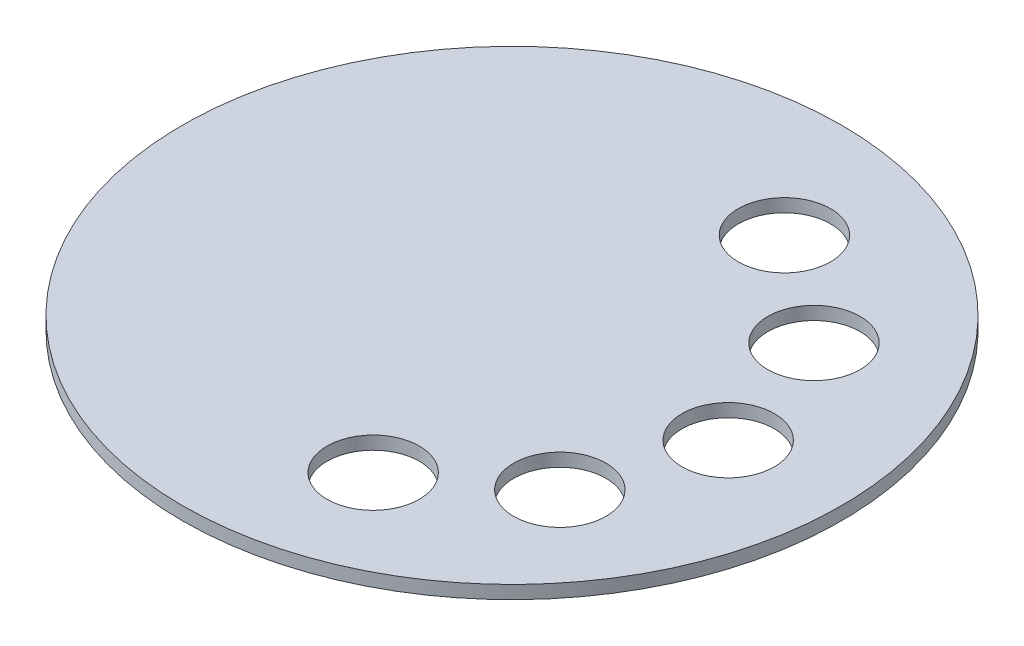
SolidWorks part; units mm, degrees
ref_plane "Front Plane" through (0, 0, 0) normal (0, 0, 1) x (1, 0, 0)
ref_plane "Top Plane" through (0, 0, 0) normal (0, 1, 0) x (1, 0, 0)
ref_plane "Right Plane" through (0, 0, 0) normal (1, 0, 0) x (0, 0, -1)
sketch "Sketch1" plane through (0, 0, 0) normal (0, 1, 0) x (1, 0, 0)
  line L0 (0, 125) -> (0, -125) construction
  line L1 (-125, 0) -> (125, 0) construction
  line L2 (-38.6271, -118.8821) -> (38.6271, 118.8821) construction
  line L3 (-38.6271, 118.8821) -> (38.6271, -118.8821) construction
  line L4 (-101.1271, -73.4732) -> (101.1271, 73.4732) construction
  line L5 (-101.1271, 73.4732) -> (101.1271, -73.4732) construction
  line L6 (0, 125) -> (0, -125)
  circle A0 centre (0, 0) radius 125
  circle A2 centre (25.3394, 77.9866) radius 17.5
  circle A3 centre (66.3394, 48.1984) radius 17.5
  circle A4 centre (82, 0) radius 17.5
  circle A5 centre (66.3394, -48.1984) radius 17.5
  circle A6 centre (25.3394, -77.9866) radius 17.5
  dimension "D1" = 18
  dimension "D3" = 36
  dimension "D5" = 35
  dimension "D6" = 35
  dimension "D7" = 35
  dimension "D8" = 35
  dimension "D9" = 35
  dimension "D10" = 250
  dimension "D2" = 18
  dimension "D4" = 36
  dimension "D11" = 43
  dimension "D12" = 43
  dimension "D13" = 43
  dimension "D14" = 43
  dimension "D15" = 43
extrude "Boss-Extrude1" add sketch "Sketch1" along normal blind 5 contours A0
extrude "Cut-Extrude4" cut sketch "Sketch1<5>" along normal blind 10 contours A2 | A6 | A5 | A4 | A3
sketch "Sketch1<5>" plane through (0, 0, 0) normal (0, 1, 0) x (1, 0, 0) same geometry as "Sketch1"
